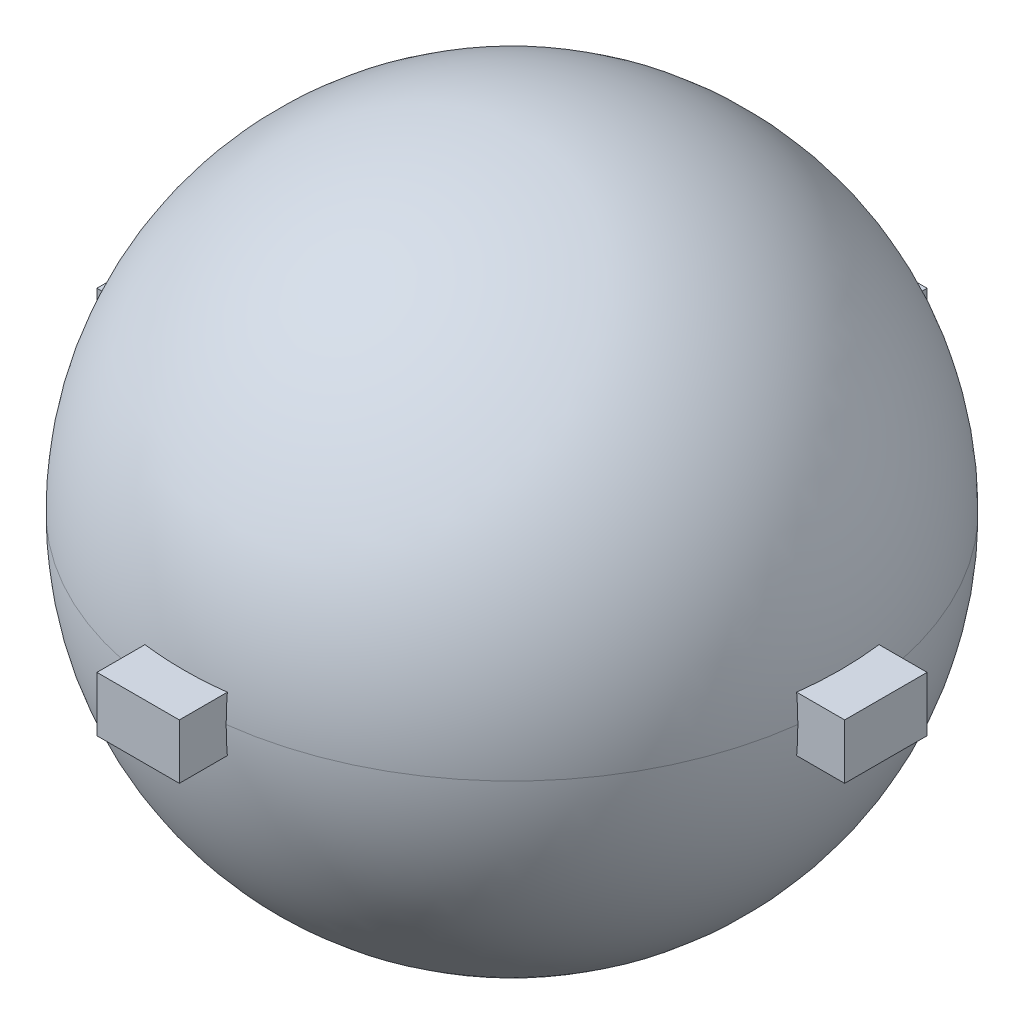
SolidWorks part; units mm, degrees
ref_plane "Front Plane" through (0, 0, 0) normal (0, 0, 1) x (1, 0, 0)
ref_plane "Top Plane" through (0, 0, 0) normal (0, 1, 0) x (1, 0, 0)
ref_plane "Right Plane" through (0, 0, 0) normal (1, 0, 0) x (0, 0, -1)
sketch "Sketch1" plane through (0, 0, 0) normal (0, 1, 0) x (1, 0, 0)
  circle A0 centre (0, 0) radius 304.8
  dimension "D1" = 609.6
extrude "Boss-Extrude1" add sketch "Sketch1" along normal blind 609.6
fillet "Fillet1" radius 304.8 2 edges at (0, 0, 304.8) (0, 609.6, 304.8)
shell "Shell2" thickness 3.175
ref_plane "Plane1" through (0, 304.8, 0) normal (0, 1, 0) x (1, 0, 0)
sketch "Sketch2" plane through (0, 304.8, 0) normal (0, 1, 0) x (1, 0, 0)
  line L0 (0, 0) -> (360.045, 0) construction
  line L1 (360.045, -63.5) -> (360.045, 63.5)
  point P5 (360.045, 0)
  dimension "D1" = 360.045
  dimension "D2" = 127
ref_plane "Plane2" through (345.7575, 0, 0) normal (1, 0, 0) x (0, 0, -1)
sketch "Sketch3" plane through (345.7575, 0, 0) normal (1, 0, 0) x (0, 0, -1)
  line L1 (-38.1, 279.4) -> (38.1, 279.4)
  line L2 (-38.1, 279.4) -> (-38.1, 330.2)
  line L3 (-38.1, 330.2) -> (38.1, 330.2)
  line L4 (38.1, 279.4) -> (38.1, 330.2)
  line L5 (-38.1, 279.4) -> (38.1, 330.2) construction
  line L6 (-38.1, 330.2) -> (38.1, 279.4) construction
  point P0 (0, 304.8)
  dimension "D1" = 50.8
  dimension "D2" = 76.2
extrude "Boss-Extrude2" add sketch "Sketch3" against normal up to surface (44.4167 mm away) up to face at (0, 304.8, -304.8)
pattern_circular "CirPattern1" count 4 over 360 about axis through (0, 304.8, 0) along (0, -1, 0) of "Boss-Extrude2"
